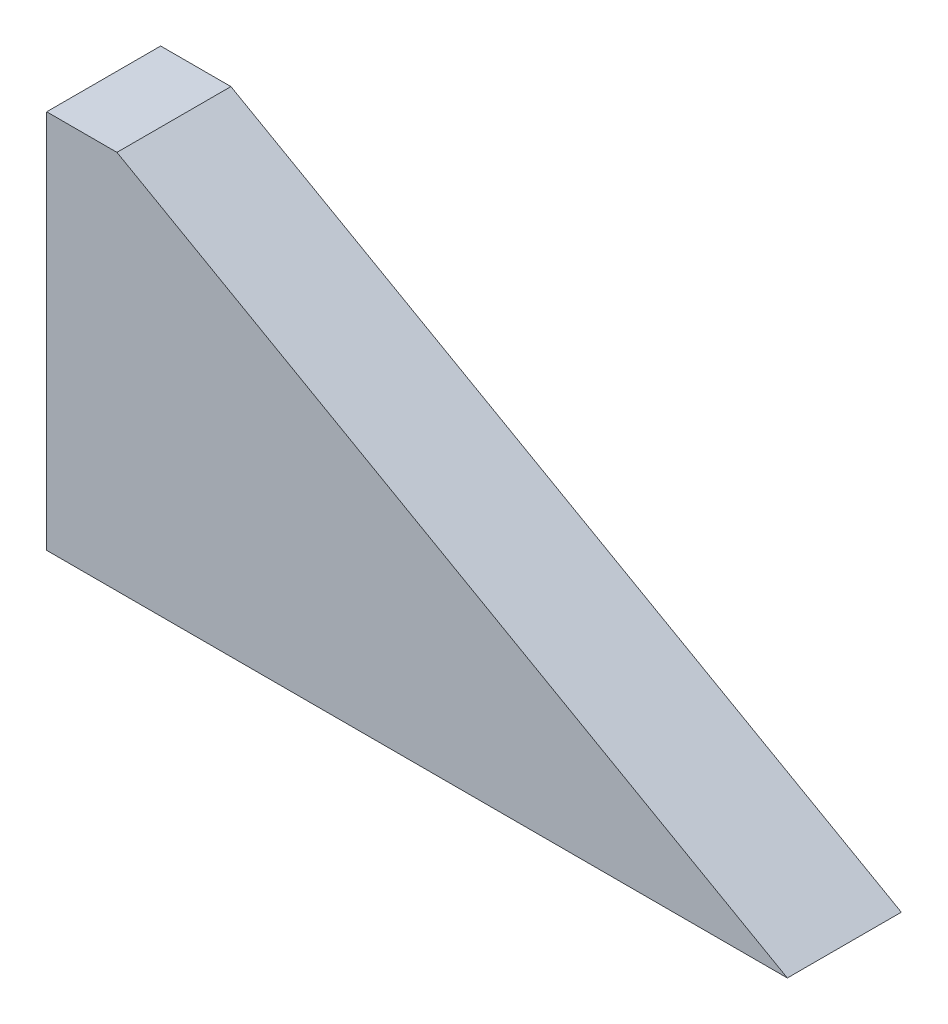
SolidWorks part; units mm, degrees
material "Клен"
ref_plane "Спереди" through (0, 0, 0) normal (0, 0, 1) x (1, 0, 0)
ref_plane "Сверху" through (0, 0, 0) normal (0, 1, 0) x (1, 0, 0)
ref_plane "Справа" through (0, 0, 0) normal (1, 0, 0) x (0, 0, -1)
sketch "Эскиз1" plane through (0, 0, 0) normal (0, 0, 1) x (1, 0, 0)
  line L0 (6, 6.0784) -> (6, 26.0784)
  line L2 (6, 26.0784) -> (9.7, 26.0784)
  line L3 (45, 6.0784) -> (6, 6.0784)
  line L4 (9.7, 26.0784) -> (45, 6.0784)
extrude "Бобышка-Вытянуть1" add sketch "Эскиз1" against normal blind 6
